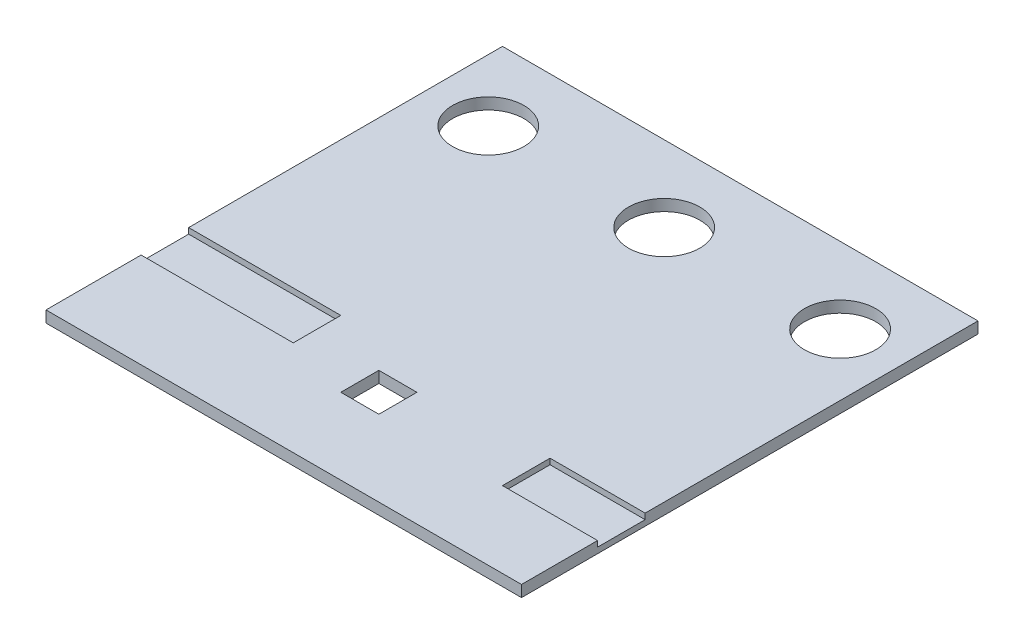
SolidWorks part; units mm, degrees
ref_plane "Front Plane" through (0, 0, 0) normal (0, 0, 1) x (1, 0, 0)
ref_plane "Top Plane" through (0, 0, 0) normal (0, 1, 0) x (1, 0, 0)
ref_plane "Right Plane" through (0, 0, 0) normal (1, 0, 0) x (0, 0, -1)
sketch "Sketch1" plane through (0, 0, 0) normal (0, 1, 0) x (1, 0, 0)
  line L0 (0, 0) -> (0, 50000) construction
  line L2 (-25, -40) -> (25, -40)
  line L3 (-25, -40) -> (-25, 8)
  line L4 (-25, 8) -> (25, 8)
  line L5 (25, -40) -> (25, 8)
  line L6 (-25, -40) -> (25, 8) construction
  line L7 (-25, 8) -> (25, -40) construction
  line L8 (-25, -30) -> (-9, -30)
  line L9 (-25, -30) -> (-25, -25)
  line L10 (-25, -25) -> (-9, -25)
  line L11 (-9, -30) -> (-9, -25)
  line L12 (-25, -30) -> (-9, -25) construction
  line L13 (-25, -25) -> (-9, -30) construction
  line L14 (15, -32) -> (25, -32)
  line L15 (15, -32) -> (15, -27)
  line L16 (15, -27) -> (25, -27)
  line L17 (25, -32) -> (25, -27)
  line L18 (15, -32) -> (25, -27) construction
  line L19 (15, -27) -> (25, -32) construction
  line L20 (-2, -32) -> (2, -32)
  line L21 (-2, -32) -> (-2, -28)
  line L22 (-2, -28) -> (2, -28)
  line L23 (2, -32) -> (2, -28)
  line L24 (-2, -32) -> (2, -28) construction
  line L25 (-2, -28) -> (2, -32) construction
  circle A0 centre (0, 0) radius 3.75
  circle A1 centre (18.5, 0) radius 3.75
  circle A2 centre (-18.5, 0) radius 3.75
  point P9 (0, -16)
  point P14 (-17, -27.5)
  point P19 (20, -29.5)
  point P25 (0, -30)
  dimension "D2" = 7.5
  dimension "D3" = 18.5
  dimension "D4" = 40
  dimension "D5" = 8
  dimension "D6" = 50
  dimension "D7" = 32
  dimension "D8" = 5
  dimension "D9" = 30
  dimension "D10" = 5
  dimension "D11" = 10
  dimension "D12" = 16
  dimension "D13" = 30
  dimension "D14" = 4
  dimension "D1" = 2
extrude "Boss-Extrude1" add sketch "Sketch1" along normal blind 1.2 contours L15 L16 L5 L4 L3 L10 L11 L8 L2 L14 A0 A1 A2 region at (0.1697, 0, 16.1422)
extrude "Boss-Extrude3" add sketch "Sketch1<5>" along normal blind 0.6 contours L8 L11 L10 L3 | L16 L15 L14 L5 region at (-17, 0, 27.5) region at (20, 0, 29.5)
sketch "Sketch1<5>" plane through (0, 0, 0) normal (0, 1, 0) x (1, 0, 0) same geometry as "Sketch1"
